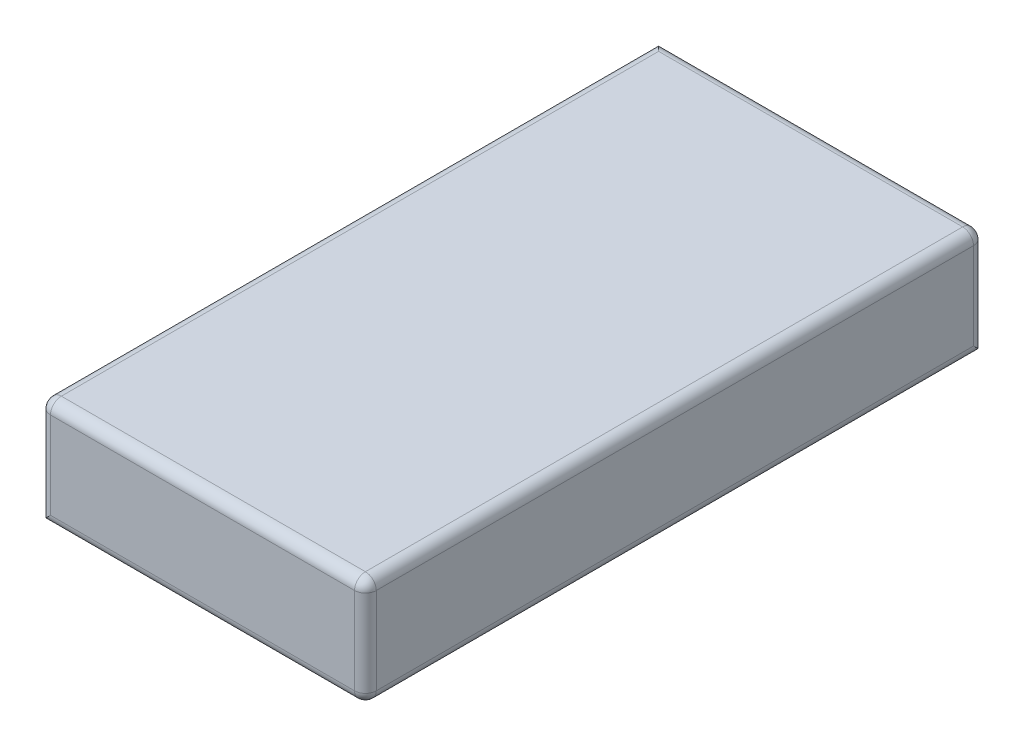
SolidWorks part; units mm, degrees
ref_plane "Front Plane" through (0, 0, 0) normal (0, 0, 1) x (1, 0, 0)
ref_plane "Top Plane" through (0, 0, 0) normal (0, 1, 0) x (1, 0, 0)
ref_plane "Right Plane" through (0, 0, 0) normal (1, 0, 0) x (0, 0, -1)
sketch "Sketch1" plane through (0, 0, 0) normal (0, 0, 1) x (1, 0, 0)
  line L1 (-15, 5) -> (15, 5)
  line L2 (-15, 5) -> (-15, -5)
  line L3 (-15, -5) -> (15, -5)
  line L4 (15, 5) -> (15, -5)
  line L5 (-15, 5) -> (15, -5) construction
  line L6 (-15, -5) -> (15, 5) construction
  point P0 (0, 0)
  dimension "D1" = 10
  dimension "D2" = 30
extrude "Boss-Extrude1" add sketch "Sketch1" along normal blind 57
fillet "Fillet1" radius 1 9 edges at (15, 0, 0) (0, 5, 0) (15, 0, 57) (0, 5, 57) (-15, 0, 57) (0, -5, 57) (15, -5, 28.5) (-15, 5, 28.5) (15, 5, 28.5)
